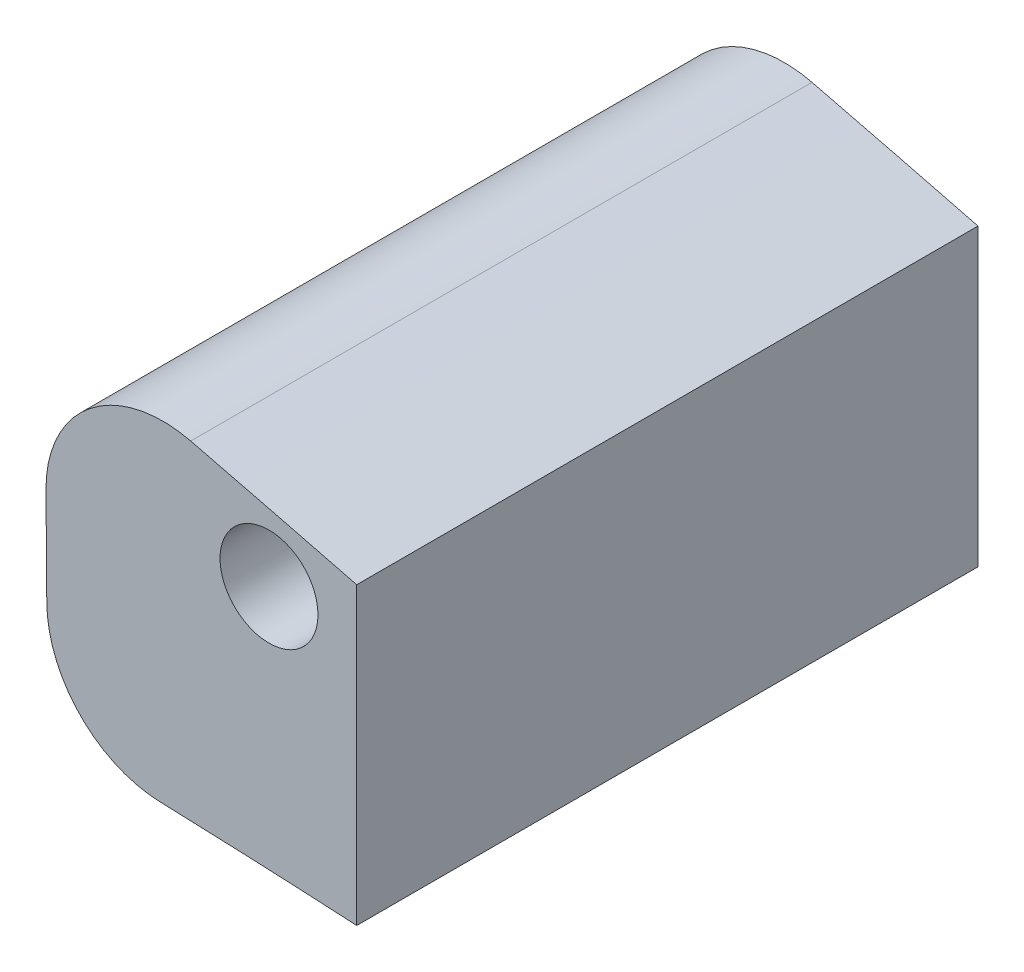
SolidWorks part; units mm, degrees
ref_plane "Front Plane" through (0, 0, 0) normal (0, 0, 1) x (1, 0, 0)
ref_plane "Top Plane" through (0, 0, 0) normal (0, 1, 0) x (1, 0, 0)
ref_plane "Right Plane" through (0, 0, 0) normal (1, 0, 0) x (0, 0, -1)
sketch "Sketch1" plane through (0, 0, 0) normal (0, 0, 1) x (1, 0, 0)
  line L0 (-30.4002, 5.4683) -> (-30.366, 1.2404)
  circle A0 centre (-20.7128, 6.6685) radius 2.127
  arc A1 (-30.366, 1.2404) -> (-25.4592, -3.7955) centre (-25.2861, 1.2815) ccw
  arc A2 (-24.1132, 10.4439) -> (-30.4002, 5.4683) centre (-25.3203, 5.5094) ccw
  spline S0 degree 3 poles (-25.4592, -3.7955) (-20.4408, -3.9666) (-12.7271, -4.3597) (0.908, -5.5793) (12.5232, -6.1737) (25.8856, -7.8882) (33.395, -8.2966) (37.8389, -9.3683) knots 0 0 0 0 0.159193 0.244902 0.434077 0.527702 0.672025 0.672025 0.672025 0.672025
  spline S1 degree 3 poles (37.8389, -9.3683) (41.585, -9.7268) (31.3567, -6.1204) (23.1103, -2.9263) (1.5407, 3.8599) (-14.4379, 8.0769) (-24.1132, 10.4439) knots 0.330745 0.330745 0.330745 0.330745 0.39066 0.506531 0.70002 1 1 1 1
extrude "Boss-Extrude1" add sketch "Sketch1" along normal blind 26.9875
sketch "Sketch2" plane through (0, 0, 26.9875) normal (0, 0, 1) x (1, 0, 0)
  line L1 (-16.9028, 14.1313) -> (50.1813, 14.1313)
  line L2 (-16.9028, 14.1313) -> (-16.9028, -20.6835)
  line L3 (-16.9028, -20.6835) -> (50.1813, -20.6835)
  line L4 (50.1813, 14.1313) -> (50.1813, -20.6835)
  circle A0 centre (-20.7128, 6.6685) radius 2.127 construction
  dimension "D1" = 3.81
extrude "Cut-Extrude1" cut sketch "Sketch2" against normal through all
